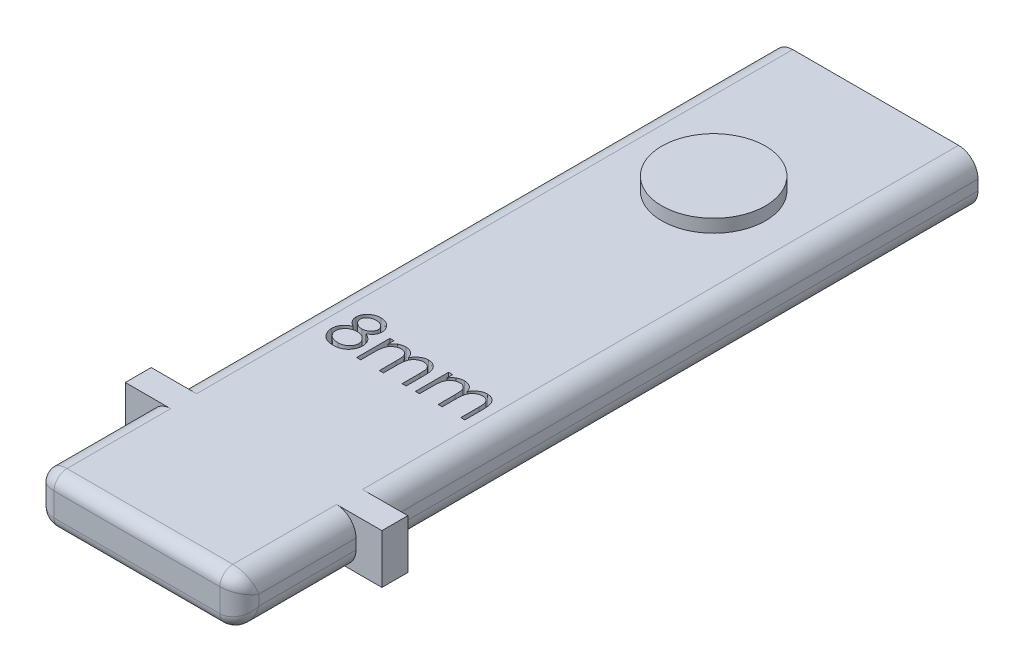
SolidWorks part; units mm, degrees
ref_plane "Front Plane" through (0, 0, 0) normal (0, 0, 1) x (1, 0, 0)
ref_plane "Top Plane" through (0, 0, 0) normal (0, 1, 0) x (1, 0, 0)
ref_plane "Right Plane" through (0, 0, 0) normal (1, 0, 0) x (0, 0, -1)
sketch "Sketch2" plane through (0, 0, 0) normal (0, 1, 0) x (1, 0, 0)
  line L1 (0, 0) -> (15.8, 0)
  line L2 (0, 0) -> (0, 57)
  line L3 (0, 57) -> (15.8, 57)
  line L4 (15.8, 0) -> (15.8, 57)
  dimension "D1" = 57
  dimension "D2" = 15.8
extrude "Boss-Extrude1" add sketch "Sketch2" along normal blind 3.8
fillet "Fillet3" radius 1 2 edges at (7.9, 0, 0) (7.9, 3.8, 0)
sketch "Sketch5" plane through (0, 3.8, 0) normal (0, 1, 0) x (1, 0, 0)
  line L0 (15.8, 57) -> (0, 57) construction
  circle A0 centre (7.9, 44.5) radius 4
  point P4 (7.9, 57)
  dimension "D1" = 8
  dimension "D2" = 12.5
extrude "Boss-Extrude4" add sketch "Sketch5" along normal blind 1
sketch "Sketch6" plane through (15.8, 0, 0) normal (1, 0, 0) x (0, 0, -1)
  line L0 (9, 3.8) -> (9, 0)
  line L1 (1, 3.8) -> (57, 3.8) construction
  line L2 (1, 0) -> (57, 0) construction
  line L3 (9, 0) -> (11, 0)
  line L4 (11, 0) -> (11, 3.8)
  line L5 (11, 3.8) -> (9, 3.8)
  line L6 (0, 2.8) -> (0, 1) construction
  dimension "D1" = 9
  dimension "D2" = 2
extrude "Boss-Extrude5" add sketch "Sketch6" along normal blind 2
sketch "Sketch7" plane through (0, 0, 0) normal (-1, 0, 0) x (0, 0, 1)
  line L0 (-57, 0) -> (-1, 0) construction
  line L1 (-9, 0) -> (-11, 0)
  line L2 (-9, 0) -> (-9, 3.8)
  line L3 (-9, 3.8) -> (-11, 3.8)
  line L4 (-11, 0) -> (-11, 3.8)
  line L5 (-57, 3.8) -> (-1, 3.8) construction
  line L6 (0, 2.8) -> (0, 1) construction
  dimension "D1" = 9
  dimension "D2" = 2
extrude "Boss-Extrude6" add sketch "Sketch7" along normal blind 2
fillet "Fillet4" radius 1.5 14 edges at (0, 0.2929, -0.2929) (0, 1.9, 0) (0, 3.5071, -0.2929) (15.8, 0.2929, -0.2929) (15.8, 1.9, 0) (15.8, 3.5071, -0.2929) (0, 0, -34) (0, 0, -5) (0, 3.8, -5) (0, 3.8, -34) (15.8, 0, -34) (15.8, 3.8, -34) (15.8, 0, -5) (15.8, 3.8, -5)
sketch "Sketch9" plane through (0, 3.8, 0) normal (0, 1, 0) x (1, 0, 0)
  text T0 "8mm\r\n"
extrude "Cut-Extrude1" cut sketch "Sketch9" against normal blind 5
